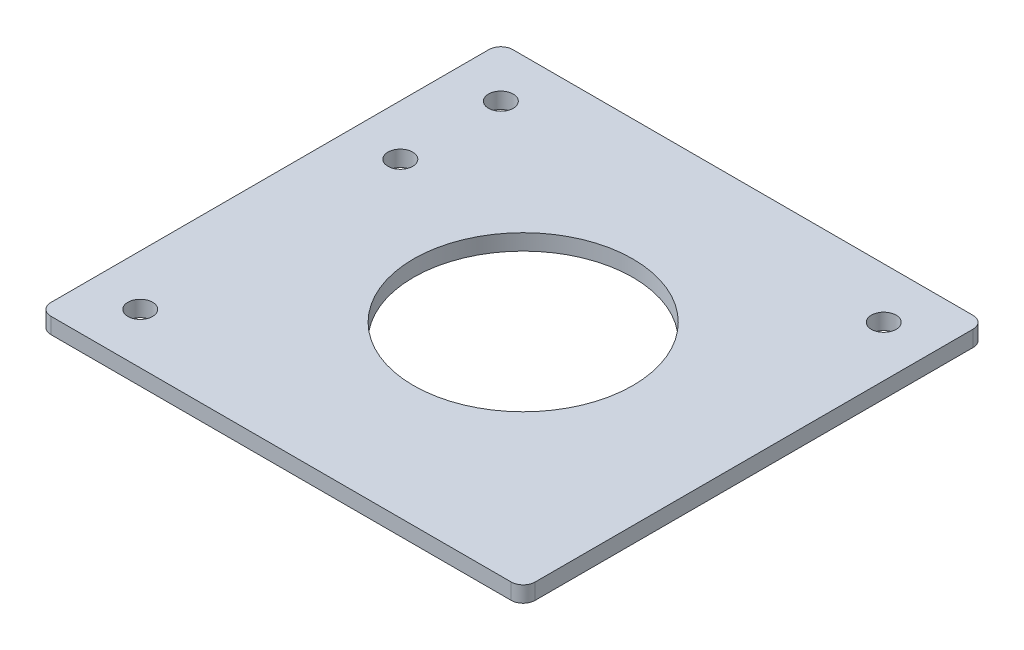
SolidWorks part; units mm, degrees
ref_plane "Front Plane" through (0, 0, 0) normal (0, 0, 1) x (1, 0, 0)
ref_plane "Top Plane" through (0, 0, 0) normal (0, 1, 0) x (1, 0, 0)
ref_plane "Right Plane" through (0, 0, 0) normal (1, 0, 0) x (0, 0, -1)
sketch "Sketch1" plane through (0, 0, 0) normal (0, 1, 0) x (1, 0, 0)
  line L0 (0.7175, -90.4) -> (88.7175, -90.4) construction
  line L1 (0.7175, 0) -> (122.1175, 0)
  line L3 (0.7175, -115.8) -> (122.1175, -115.8)
  line L4 (122.1175, 0) -> (122.1175, -115.8)
  line L5 (-27.2825, -90.4) -> (88.7175, -90.4) construction
  line L6 (88.7175, -90.4) -> (96.7175, -82.4) construction
  line L7 (96.7175, -82.4) -> (96.7175, -33.4) construction
  line L12 (96.7175, -33.4) -> (88.7175, -25.4) construction
  line L13 (88.7175, -25.4) -> (0.7175, -25.4) construction
  line L14 (88.7175, -25.4) -> (-27.2825, -25.4) construction
  line L16 (13.4175, -12.7) -> (0.7175, -12.7) construction
  line L17 (13.4175, -12.7) -> (13.4175, 0) construction
  line L18 (109.4175, -12.7) -> (109.4175, 0) construction
  line L19 (109.4175, -12.7) -> (122.1175, -12.7) construction
  line L20 (13.4175, -103.1) -> (0.7175, -103.1) construction
  line L21 (13.4175, -103.1) -> (13.4175, -100) construction
  line L22 (13.4175, -103.1) -> (13.4175, -115.8) construction
  line L23 (13.4175, -12.7) -> (16.5175, -12.7) construction
  line L24 (0.7175, -35.9) -> (16.9175, -35.9) construction
  line L25 (109.4175, -12.7) -> (109.4175, -15.8) construction
  line L30 (0.7175, 0) -> (0.7175, -115.8)
  line L31 (16.9175, -35.9) -> (-25.2825, -35.9) construction
  line L32 (13.4175, -37.9) -> (16.5175, -37.9) construction
  line L35 (-25.2825, -39.9) -> (16.9175, -39.9) construction
  line L36 (0.7175, -39.9) -> (16.9175, -39.9) construction
  line L37 (13.4175, -35.9) -> (13.4175, -39.9) construction
  line L38 (13.4175, -37.9) -> (0.7175, -37.9) construction
  circle A0 centre (64.2175, -57.9) radius 27.5
  circle A1 centre (13.4175, -12.7) radius 3.1
  circle A2 centre (109.4175, -12.7) radius 3.1
  circle A4 centre (13.4175, -103.1) radius 3.1
  arc A5 (16.9175, -39.9) -> (16.9175, -35.9) centre (16.9175, -37.9) ccw construction
  circle A6 centre (13.4175, -37.9) radius 3.1
  point P38 (13.4175, -37.9)
  dimension "D4" = 55
  dimension "D5" = 88
  dimension "D6" = 6.2
  dimension "D1" = 25.4
  dimension "D2" = 25.4
  dimension "D3" = 25.4
  dimension "D7" = 12.7
extrude "Boss-Extrude1" add sketch "Sketch1" along normal blind 4
fillet "Fillet1" radius 3 4 edges at (122.1175, 2, 0) (122.1175, 2, 115.8) (0.7175, 2, 115.8) (0.7175, 2, 0)
